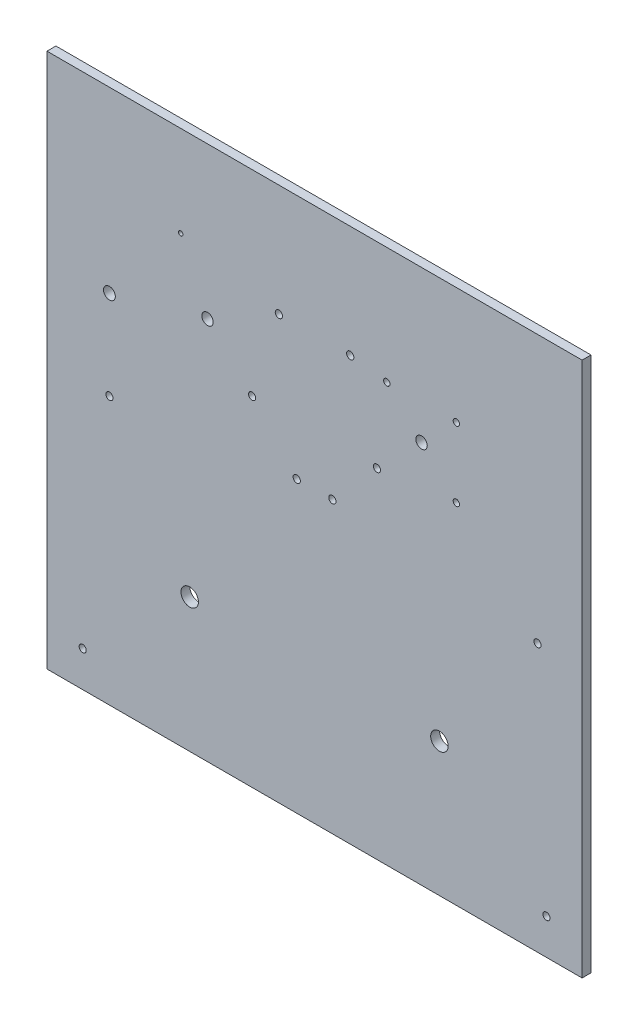
SolidWorks part; units mm, degrees
material "1060 Alloy"
ref_plane "Front Plane" through (0, 0, 0) normal (0, 0, 1) x (1, 0, 0)
ref_plane "Top Plane" through (0, 0, 0) normal (0, 1, 0) x (1, 0, 0)
ref_plane "Right Plane" through (0, 0, 0) normal (1, 0, 0) x (0, 0, -1)
sketch "Sketch1" plane through (0, 0, 0) normal (0, 0, 1) x (1, 0, 0)
  line L0 (-25.4, 301.365) -> (25.4, 301.365) construction
  line L1 (0, 381) -> (0, 0) construction
  line L2 (-146.05, 190.5) -> (-146.05, -8.5714) construction
  line L3 (51.4513, 297.7987) -> (100.9487, 248.3013) construction
  line L4 (76.2, 273.05) -> (100.9487, 297.7987) construction
  line L6 (190.5, 381) -> (-190.5, 381)
  line L10 (-76.2, 273.05) -> (76.2, 273.05) construction
  line L11 (-44.45, 241.3) -> (44.45, 241.3) construction
  line L12 (-12.7, 206.115) -> (12.7, 206.115) construction
  line L13 (190.5, 381) -> (190.5, 0)
  line L14 (-190.5, 381) -> (-190.5, 0)
  line L16 (-190.5, 0) -> (190.5, 0)
  circle A0 centre (76.2, 273.05) radius 4.064
  circle A1 centre (44.45, 241.3) radius 2.54
  circle A2 centre (88.9, 95.25) radius 6.223
  circle A3 centre (-165.1, 25.4) radius 2.54
  circle A4 centre (100.9487, 297.7987) radius 2.25
  circle A5 centre (158.75, 190.5) radius 2.54
  circle A6 centre (51.4513, 297.7987) radius 2.25
  circle A7 centre (165.1, 25.4) radius 2.54
  circle A8 centre (-88.9, 95.25) radius 6.223
  circle A9 centre (12.7, 206.115) radius 2.5797
  circle A10 centre (-146.05, 190.5) radius 2.54
  circle A12 centre (-25.4, 301.365) radius 2.5797
  circle A13 centre (25.4, 301.365) radius 2.5797
  circle A14 centre (-44.45, 241.3) radius 2.54
  circle A15 centre (-76.2, 273.05) radius 4.064
  circle A16 centre (-12.7, 206.115) radius 2.5797
  circle A17 centre (-95.25, 316.23) radius 1.5875
  circle A19 centre (100.9487, 248.3013) radius 2.25
  circle A20 centre (51.4513, 248.3013) radius 2.25 [skipped]
  point P4 (0, 301.365)
  point P6 (0, 241.3)
  point P18 (0, 273.05)
  point P38 (0, 206.115)
  dimension "D2" = 50.8
  dimension "D18" = 5.1594
  dimension "D13" = 4
  dimension "D4" = 381
  dimension "D5" = 381
  dimension "D6" = 25.4
  dimension "D7" = 25.4
  dimension "D8" = 95.25
  dimension "D9" = 101.6
  dimension "D10" = 190.5
  dimension "D11" = 44.45
  dimension "D12" = 114.3
  dimension "D14" = 49.4975
  dimension "D15" = 273.05
  dimension "D16" = 241.3
  dimension "D17" = 146.05
  dimension "D19" = 316.23
  dimension "D20" = 95.25
  dimension "D21" = 31.75
  dimension "D22" = 190.5
  dimension "D23" = 95.25
extrude "Boss-Extrude1" add sketch "Sketch1" along normal blind 6.35
hole_wizard "3/8-24 Tapped Hole2" positions "Sketch5" profile "Sketch4" tap size "3/8-24" standard "Ansi Inch" end condition through all
sketch "Sketch5" plane through (0, 0, 6.35) normal (0, 0, 1) x (1, 0, 0)
  line L0 (-146.05, 190.5) -> (-146.05, 254) construction
  point P0 (-146.05, 254)
  dimension "D1" = 63.5
sketch "Sketch4" plane through (-146.05, 254, 6.35) normal (1, 0, 0) x (0, -1, 0)
  line L0 (0, 0) -> (0, 6.35)
  line L1 (0, 6.35) -> (4.2164, 6.35)
  line L2 (4.2164, 6.35) -> (4.2164, 0)
  line L5 (4.2164, 0) -> (0, 0)
  line L11 (0, -6.35) -> (0, 107.95) construction
  dimension "Thru Tap Drill Dia." = 8.4328
  dimension "Thru Tap Drill Depth" = 6.35
cosmetic thread "Hole Thread1" parameters "D2"=9.525
